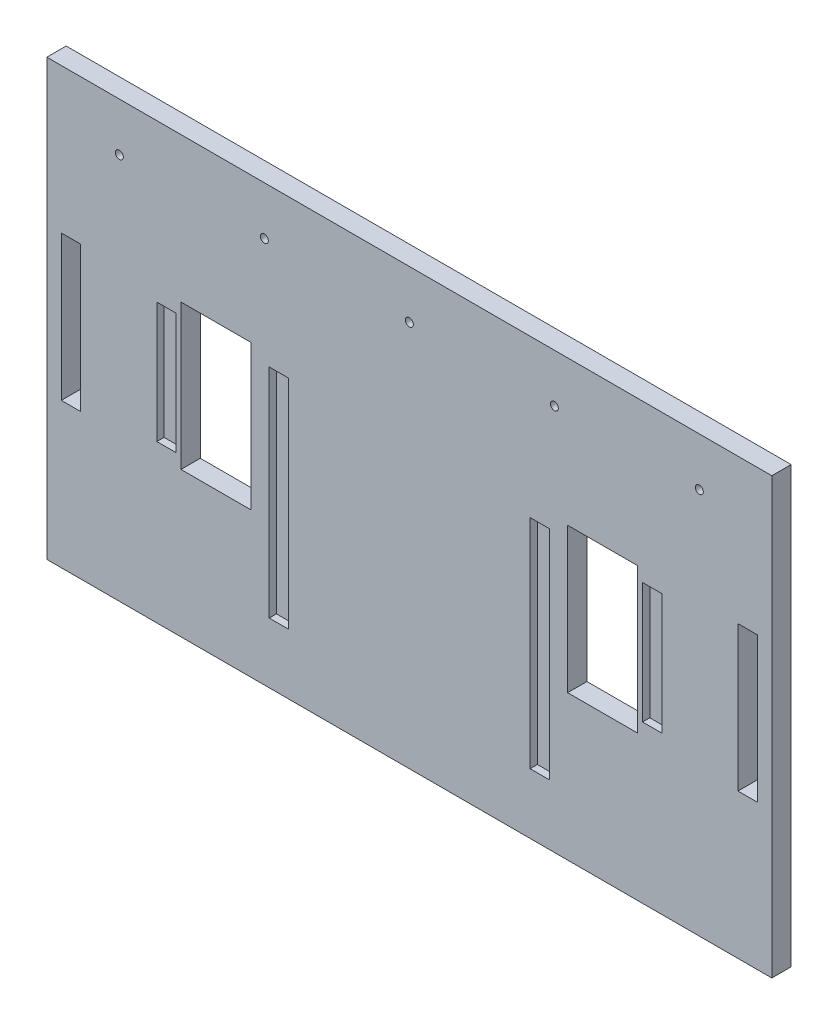
SolidWorks part; units mm, degrees
ref_plane "Front" through (0, 0, 0) normal (0, 0, 1) x (1, 0, 0)
ref_plane "Top" through (0, 0, 0) normal (0, 1, 0) x (1, 0, 0)
ref_plane "Right" through (0, 0, 0) normal (1, 0, 0) x (0, 0, -1)
sketch "Esquisse1" plane through (0, 0, 0) normal (0, 0, 1) x (1, 0, 0)
  line L1 (0, 0) -> (300, 0)
  line L2 (0, 0) -> (0, 180)
  line L3 (0, 180) -> (300, 180)
  line L4 (300, 0) -> (300, 180)
  dimension "D1" = 300
  dimension "D2" = 180
extrude "Boss.-Extru.1" add sketch "Esquisse1" along normal blind 8
sketch "Esquisse2" plane through (0, 0, 8) normal (0, 0, 1) x (1, 0, 0)
  line L0 (150, 180) -> (150, 0) construction
  line L1 (55.5, 60) -> (84.5, 60)
  line L2 (55.5, 60) -> (55.5, 120)
  line L3 (55.5, 120) -> (84.5, 120)
  line L4 (84.5, 60) -> (84.5, 120)
  line L5 (300, 180) -> (0, 180) construction
  line L6 (0, 0) -> (300, 0) construction
  line L7 (84.5, 90) -> (150, 90) construction
  line L8 (70, 60) -> (70, 120) construction
  line L9 (55.5, 90) -> (14, 90) construction
  line L10 (10, 60) -> (10, 120) construction
  line L11 (6, 60) -> (14, 60)
  line L12 (6, 60) -> (6, 120)
  line L13 (6, 120) -> (14, 120)
  line L14 (14, 60) -> (14, 120)
  line L15 (290, 60) -> (290, 120) construction
  line L16 (244.5, 90) -> (286, 90) construction
  line L17 (230, 60) -> (230, 120) construction
  line L18 (286, 60) -> (286, 120)
  line L19 (294, 120) -> (286, 120)
  line L20 (294, 60) -> (294, 120)
  line L21 (294, 60) -> (286, 60)
  line L22 (215.5, 60) -> (215.5, 120)
  line L23 (244.5, 120) -> (215.5, 120)
  line L24 (244.5, 60) -> (244.5, 120)
  line L25 (244.5, 60) -> (215.5, 60)
  dimension "D1" = 90
  dimension "D2" = 60
  dimension "D3" = 29
  dimension "D4" = 160
  dimension "D5" = 8
  dimension "D6" = 60
  dimension "D7" = 280
extrude "Enlèv. mat.-Extru.1" cut sketch "Esquisse2" against normal through all
sketch "Esquisse3" plane through (0, 0, 8) normal (0, 0, 1) x (1, 0, 0)
  line L0 (0, 160) -> (300, 160) construction
  line L1 (0, 180) -> (0, 0) construction
  line L2 (300, 0) -> (300, 180) construction
  line L3 (180, 160) -> (180, 172.6988) construction
  line L4 (300, 180) -> (0, 180) construction
  line L5 (150, 160) -> (150, 176.3559) construction
  circle A0 centre (270, 160) radius 1.65
  circle A1 centre (210, 160) radius 1.65
  circle A2 centre (150, 160) radius 1.65
  circle A3 centre (90, 160) radius 1.65
  circle A4 centre (30, 160) radius 1.65
  dimension "D1" = 3.3
  dimension "D2" = 60
  dimension "D3" = 60
  dimension "D5" = 60
  dimension "D4" = 20
extrude "Enlèv. mat.-Extru.2" cut sketch "Esquisse3" against normal up to vertex (8 mm away) up to point (300, 180, 0)
sketch "Esquisse4" plane through (0, 0, 8) normal (0, 0, 1) x (1, 0, 0)
  line L0 (150, 0) -> (150, 180) construction
  line L1 (92, 115) -> (100, 115)
  line L2 (92, 115) -> (92, 25)
  line L3 (92, 25) -> (100, 25)
  line L4 (100, 115) -> (100, 25)
  line L5 (0, 0) -> (300, 0) construction
  line L6 (300, 180) -> (0, 180) construction
  line L7 (55.5, 60) -> (84.5, 60) construction
  line L8 (84.5, 60) -> (84.5, 120) construction
  line L9 (200, 115) -> (200, 25)
  line L10 (208, 25) -> (200, 25)
  line L11 (208, 115) -> (208, 25)
  line L12 (208, 115) -> (200, 115)
  line L13 (55.5, 120) -> (55.5, 60) construction
  line L14 (45.5, 115) -> (53.5, 115)
  line L15 (45.5, 115) -> (45.5, 65)
  line L16 (45.5, 65) -> (53.5, 65)
  line L17 (53.5, 115) -> (53.5, 65)
  line L18 (53.5, 90) -> (55.5, 90) construction
  line L19 (246.5, 90) -> (244.5, 90) construction
  line L20 (246.5, 115) -> (246.5, 65)
  line L21 (254.5, 65) -> (246.5, 65)
  line L22 (254.5, 115) -> (254.5, 65)
  line L23 (254.5, 115) -> (246.5, 115)
  dimension "D1" = 35
  dimension "D2" = 90
  dimension "D3" = 8
  dimension "D4" = 7.5
  dimension "D5" = 8
  dimension "D6" = 2
  dimension "D7" = 50
extrude "Enlèv. mat.-Extru.3" cut sketch "Esquisse4" against normal blind 3
